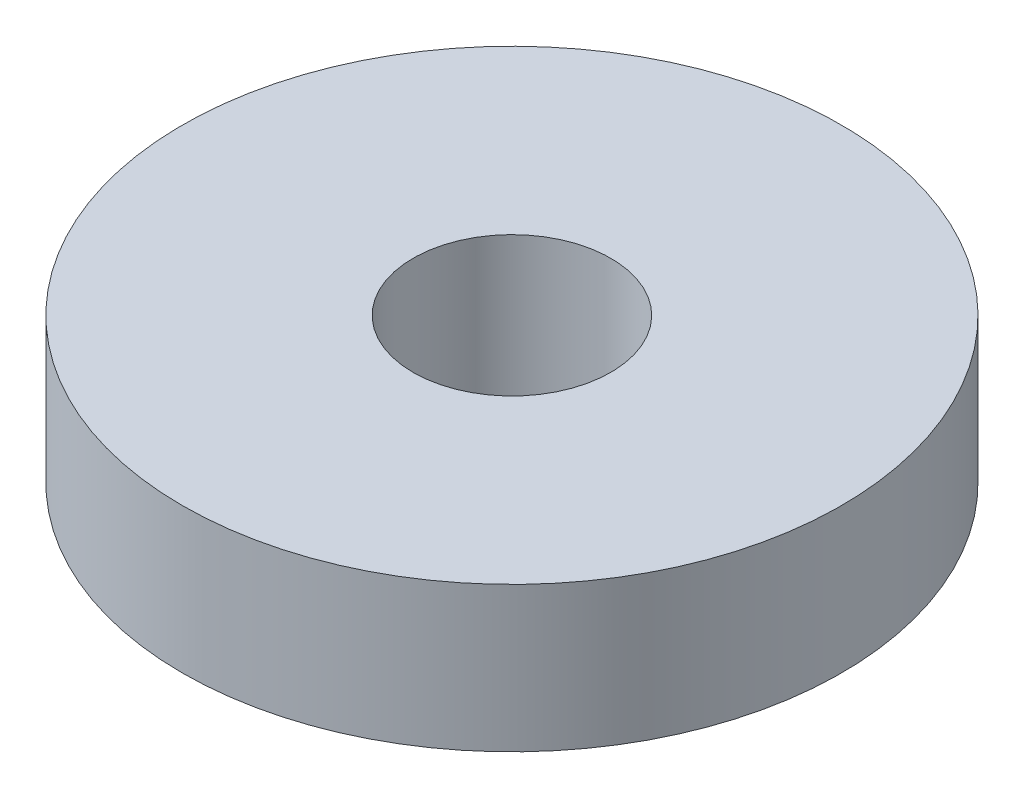
SolidWorks part; units mm, degrees
ref_plane "Front Plane" through (0, 0, 0) normal (0, 0, 1) x (1, 0, 0)
ref_plane "Top Plane" through (0, 0, 0) normal (0, 1, 0) x (1, 0, 0)
ref_plane "Right Plane" through (0, 0, 0) normal (1, 0, 0) x (0, 0, -1)
sketch "Sketch1" plane through (0, 0, 0) normal (0, 1, 0) x (1, 0, 0)
  circle A0 centre (0, 0) radius 50
  dimension "FLANGE_OD" = 100
extrude "Boss-Extrude1" add sketch "Sketch1" along normal blind 22
sketch "Sketch2" plane through (0, 0, 0) normal (0, 1, 0) x (1, 0, 0)
  circle A0 centre (0, 0) radius 15
  dimension "BORE_D" = 30
extrude "Cut-Extrude1" cut sketch "Sketch2" along normal through all
sketch "Sketch3" plane through (0, 22, 0) normal (0, 1, 0) x (1, 0, 0)
  circle A0 centre (0, 0) radius 9.3196 construction
  circle A1 centre (-9.3196, 0) radius 2.1852
  dimension "BOLT_D" = 4.3703
  dimension "BOLT_PCD" = 18.6392
extrude "Cut-Extrude2" cut sketch "Sketch3" against normal blind 20.0566 rebuild error yes
pattern_circular "CirPattern1" count 8 over 360 rebuild error yes
